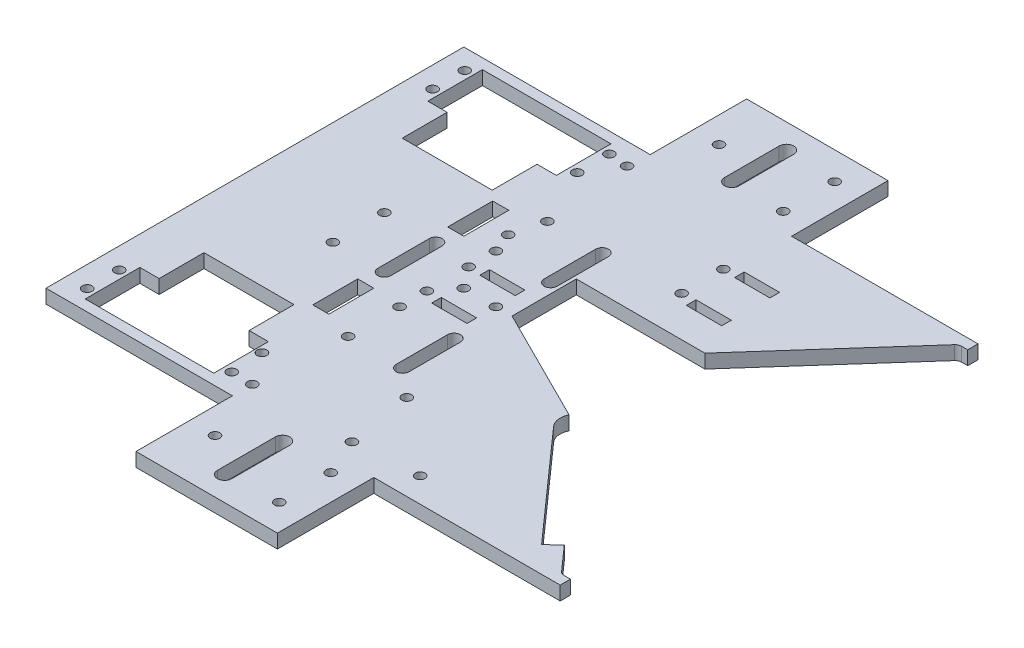
SolidWorks part; units mm, degrees
material "Acrylic (Medium-high impact)"
ref_plane "Front Plane" through (0, 0, 0) normal (0, 0, 1) x (1, 0, 0)
ref_plane "Top Plane" through (0, 0, 0) normal (0, 1, 0) x (1, 0, 0)
ref_plane "Right Plane" through (0, 0, 0) normal (1, 0, 0) x (0, 0, -1)
sketch "Sketch2" plane through (0, 0, 0) normal (0, 1, 0) x (1, 0, 0)
  line L2 (0, 0) -> (0, 65)
  line L3 (0, 65) -> (58, 65)
  line L4 (160, 0) -> (160, 65)
  line L8 (0, 0) -> (160, 0)
  line L9 (102, 65) -> (160, 65)
  line L11 (102, 65) -> (102, 95)
  line L12 (58, 65) -> (58, 95)
  line L13 (58, 95) -> (102, 95)
  dimension "D1" = 65
  dimension "D2" = 160
  dimension "D3" = 44
  dimension "D4" = 30
extrude "Boss-Extrude1" add sketch "Sketch2" along normal blind 4.3
mirror "Mirror1" about plane through (0, 4.3, 0) normal (0, 0, -1) of bodies 101
sketch "Sketch3" plane through (0, 4.3, 0) normal (0, 1, 0) x (1, 0, 0)
  line L0 (160, 61.8) -> (160, -61.8)
  line L1 (120.0126, 20) -> (157.1565, 61.8)
  line L3 (80.0126, 0) -> (80.0126, 20)
  line L4 (80.0126, 20) -> (120.0126, 20)
  line L12 (160, 65) -> (102, 65)
  line L13 (102, 65) -> (102, 95)
  line L15 (102, 95) -> (58, 95)
  line L16 (58, 65) -> (0, 65)
  line L17 (0, 65) -> (0, -65)
  line L18 (0, -65) -> (58, -65)
  line L20 (58, 95) -> (58, 65)
  line L22 (102, -65) -> (160, -65)
  line L23 (160, -65) -> (160, 65)
  line L36 (58, -65) -> (58, -95)
  line L38 (58, -95) -> (102, -95)
  line L39 (58, -95) -> (102, -95)
  line L40 (102, -95) -> (102, -65)
  line L42 (160, -61.8) -> (157.1556, -61.8)
  line L45 (160, 61.8) -> (157.1565, 61.8)
  line L48 (80.0126, 0) -> (120, -20)
  line L49 (120, -20) -> (157.1556, -61.8)
  line M24 (160, -65) -> (160, 65)
  dimension "D2" = 130
  dimension "D3" = 20
  dimension "D4" = 40
  dimension "D1" = 0
extrude "Cut-Extrude1" cut sketch "Sketch3" against normal blind 4.5 contours L48 L49 L1 L4 L3 M24 region at (132.7054, 4.3, -1.1594)
fillet "Fillet1" radius 2 2 edges at (157.1565, 2.15, -61.8) (157.1556, 2.15, 61.8)
ref_axis "Axis1" through (80, 4.3, 95) along (0, 0, -1)
sketch "Sketch4" plane through (0, 4.3, 0) normal (0, 1, 0) x (1, 0, 0)
  line L0 (80, -95) -> (80, 95)
  line L1 (102, -95) -> (58, -95) construction
  line L2 (102, 95) -> (58, 95) construction
ref_plane "Plane2" through (0, 4.3, 0) normal (0, 1, 0) x (1, 0, 0)
sketch "Sketch6" plane through (0, 4.3, 0) normal (0, 1, 0) x (1, 0, 0)
  line L3 (9, -61.8) -> (49, -61.8)
  line L6 (29, -45.8) -> (29, -44.8)
  line L7 (9, -44.8) -> (15, -44.8)
  line L11 (43, -44.8) -> (43, -30.8418)
  line L12 (15, -44.8) -> (15, -30.8418)
  line L13 (15, -30.8418) -> (43, -30.8418)
  line L15 (0, 0) -> (80.0126, 0)
  line L16 (80.0126, 0) -> (120, -20) construction
  line L18 (9, 44.8) -> (15, 44.8)
  line L20 (15, 30.8418) -> (43, 30.8418)
  line L21 (15, 44.8) -> (15, 30.8418)
  line L22 (43, 44.8) -> (43, 30.8418)
  line L25 (15, -45.8) -> (15, -30.8418) construction
  line L27 (9, 61.8) -> (49, 61.8)
  line L30 (4, -61.8) -> (3, -61.8)
  line L31 (0, -61.8) -> (160, -61.8) construction
  line L32 (3, -61.8) -> (4, -61.8)
  line L33 (3, -44.8) -> (3, -62.8) construction
  line L34 (3, -62.8) -> (55, -62.8) construction
  line L35 (55, -44.8) -> (55, -62.8) construction
  line L36 (4, -61.8) -> (54, -61.8) construction
  line L37 (0, 61.8) -> (160, 61.8) construction
  line L38 (54, 61.8) -> (55, 61.8)
  line L39 (54, 61.8) -> (55, 61.8)
  line L40 (43, 44.8) -> (49, 44.8)
  line L41 (4, -45.8) -> (4, -61.8) construction
  line L42 (4, -45.8) -> (54, -45.8) construction
  line L43 (43, -44.8) -> (49, -44.8)
  line L44 (3, -44.8) -> (55, -44.8) construction
  line L45 (29, -45.8) -> (29, -30.8418) construction
  line L46 (43, -45.8) -> (43, -30.8418) construction
  line L47 (54, -45.8) -> (54, -61.8) construction
  line L48 (9, -61.8) -> (49, -61.8)
  line L52 (9, 61.8) -> (9, 44.8)
  line L53 (55, 61.8) -> (54, 61.8)
  line L56 (49, 61.8) -> (49, 44.8)
  line L59 (3, -61.8) -> (4, -61.8)
  line L60 (9, -44.8) -> (9, -61.8)
  line L64 (49, -44.8) -> (49, -61.8)
  dimension "D4" = 1
  dimension "D5" = 14
  dimension "D6" = 14
extrude "Cut-Extrude2" cut sketch "Sketch6" against normal blind 10
sketch "Sketch8" plane through (0, 4.3, 0) normal (0, 1, 0) x (1, 0, 0)
  circle A0 centre (6.5, 58.8) radius 1.5
  circle A1 centre (6.5, 48.8) radius 1.5
  circle A2 centre (51.5, 48.8) radius 1.5
  circle A3 centre (51.5, 58.8) radius 1.5
  circle A4 centre (6.5, -48.7) radius 1.5
  circle A5 centre (6.5, -58.7) radius 1.5
  circle A6 centre (51.5, -58.7) radius 1.5
  circle A7 centre (51, -48.8) radius 1.5
  dimension "D7" = 3
extrude "Cut-Extrude3" cut sketch "Sketch8" against normal blind 10
sketch "Sketch9" plane through (0, 0, 0) normal (0, -1, 0) x (1, 0, 0)
  line L0 (75.75, 69.4) -> (75.75, 87.4)
  line L1 (75.75, -87.4) -> (75.75, -70.4)
  line L2 (80.25, -87.4) -> (80.25, -70.4)
  line L4 (80.25, 69.4) -> (80.25, 87.4)
  circle A0 centre (94, 70.4) radius 1.5
  circle A1 centre (66, 78.4) radius 1.5
  circle A2 centre (66, -78.4) radius 1.5
  circle A3 centre (94, -86.4) radius 1.5
  circle A4 centre (94, 86.4) radius 1.5
  circle A5 centre (94, -70.4) radius 1.5
  arc A6 (75.75, -87.4) -> (80.25, -87.4) centre (78, -87.4) ccw
  arc A7 (80.25, -70.4) -> (75.75, -70.4) centre (78, -70.4) ccw
  arc A10 (75.75, 69.4) -> (80.25, 69.4) centre (78, 69.4) ccw
  arc A12 (80.25, 87.4) -> (75.75, 87.4) centre (78, 87.4) ccw
  dimension "D1" = 3
extrude "Cut-Extrude4" cut sketch "Sketch9" against normal blind 10
sketch "Sketch7" plane through (0, 4.3, 0) normal (0, 1, 0) x (1, 0, 0)
  line L0 (0, 0) -> (80.0126, 0)
  line L1 (0, 65) -> (0, -65) construction
  line L2 (80.0126, 0) -> (80.0126, 20) construction
  line L3 (80, -95) -> (80, 95) construction
  line L4 (64, -9) -> (75, -9)
  line L5 (64, -6) -> (75, -6)
  line L6 (64, -9) -> (64, -6)
  line L7 (75, -9) -> (75, -6)
  line L8 (64, -7.5) -> (75, -7.5)
  line L9 (64, 7.5) -> (75, 7.5)
  line L10 (75, 9) -> (75, 6)
  line L11 (64, 9) -> (64, 6)
  line L12 (64, 6) -> (75, 6)
  line L13 (64, 9) -> (75, 9)
  line L14 (104.2547, 30) -> (115.2547, 30)
  line L15 (104.2547, 33) -> (115.2547, 33)
  line L16 (104.2547, 30) -> (104.2547, 33)
  line L17 (115.2547, 30) -> (115.2547, 33)
  line L20 (115.2547, 48) -> (115.2547, 45)
  line L21 (104.2547, 48) -> (104.2547, 45)
  line L22 (104.2547, 45) -> (115.2547, 45)
  line L23 (104.2547, 48) -> (115.2547, 48)
  line L24 (80.0126, 20) -> (120.0126, 20) construction
  circle A0 centre (60.0126, -6.5) radius 1.5
  circle A1 centre (60.0126, 6.5) radius 1.5
  circle A2 centre (100.2673, 32.5) radius 1.5
  circle A3 centre (100.2673, 45.5) radius 1.5
  dimension "D1" = 3
  dimension "D8" = 3
  dimension "D2" = 6.5
  dimension "D3" = 20
  dimension "D6" = 11
  dimension "D4" = 5
  dimension "D5" = 3
  dimension "D7" = 7.5
  dimension "D9" = 11
  dimension "D10" = 3
  dimension "D11" = 12
  dimension "D12" = 13
  dimension "D13" = 10
  dimension "D14" = 3.9874
  dimension "D15" = 0.5
  dimension "D16" = 0.5
  dimension "D17" = 3.9874
sketch "Sketch10" plane through (0, 4.3, 0) normal (0, 1, 0) x (1, 0, 0)
  line L0 (120, -20) -> (156.5589, -61.1287) construction
  line L1 (123.3218, -23.737) -> (149.8964, -53.6334)
  line L2 (116.263, -23.3218) -> (146.1593, -56.9552)
  line L3 (149.8964, -53.6334) -> (146.1593, -56.9552)
  line L4 (120, -20) -> (156.5589, -61.1287) construction
  line L5 (116.263, -23.3218) -> (152.8218, -64.4505) construction
  arc A0 (123.3218, -23.737) -> (116.263, -23.3218) centre (120, -20) ccw
  dimension "D1" = 5
  dimension "D2" = 45
extrude "Cut-Extrude5" cut sketch "Sketch10" against normal blind 10
sketch "Sketch11" plane through (0, 0, 0) normal (0, -1, 0) x (1, 0, 0)
  line L0 (0, 0) -> (80.0126, 0) construction
  line L1 (80, 95) -> (80, -95) construction
  line L2 (80.0126, 0) -> (0, 0)
  line L4 (75, 31.0313) -> (75, 15.0313)
  line L6 (79, 31.0313) -> (79, 15.0313)
  line L7 (79, -31.0313) -> (79, -15.0313)
  line L8 (75, -31.0313) -> (75, -15.0313)
  circle A0 centre (60, 31) radius 1.5
  circle A1 centre (60, 15) radius 1.5
  arc A2 (75, 31.0313) -> (79, 31.0313) centre (77, 31.0313) cw
  arc A3 (75, 15.0313) -> (79, 15.0313) centre (77, 15.0313) ccw
  arc A4 (75, -15.0313) -> (79, -15.0313) centre (77, -15.0313) cw
  arc A5 (75, -31.0313) -> (79, -31.0313) centre (77, -31.0313) ccw
  circle A6 centre (60, -15) radius 1.5
  circle A7 centre (60, -31) radius 1.5
  dimension "D1" = 3
  dimension "D2" = 16
  dimension "D3" = 15
  dimension "D4" = 20
  dimension "D5" = 15
  dimension "D6" = 4
extrude "Cut-Extrude6" cut sketch "Sketch11" against normal blind 10 contours L4 A3 L6 A2 | L8 A5 L7 A4 | A7 | A0 | A1 | A6 region at (77, 0, 23.0313) region at (77, 0, -23.0313) region at (60, 0, -31)
sketch "Sketch12" plane through (0, 0, 0) normal (0, -1, 0) x (-1, 0, 0)
  line L0 (0, 0) -> (-80.0126, 0) construction
  line L3 (-50.2627, -8) -> (-50.2627, 8)
  line L4 (-50.2627, 0) -> (-46.2627, 0)
  line L5 (-46.2627, -8) -> (-46.2627, 8)
  line L6 (0, 0) -> (-46.2627, 0)
  line L7 (0, 65) -> (0, -65) construction
  line L8 (-160, -61.8) -> (0, -61.8) construction
  line L9 (-80.0126, 0) -> (-50.2627, 0)
  line L10 (-80.0126, 0) -> (-115.5281, -17.7634) construction
  line L11 (-80.0126, 0) -> (-80.0126, 20) construction
  line L12 (-58, -65) -> (0, -65) construction
  line L13 (-58, 65) -> (0, 65) construction
  circle A0 centre (-32.2627, -8) radius 1.5
  circle A1 centre (-32.2627, 8) radius 1.5
  arc A2 (-46.2627, 8) -> (-50.2627, 8) centre (-48.2627, 8) ccw
  arc A3 (-50.2627, -8) -> (-46.2627, -8) centre (-48.2627, -8) ccw
  circle A5 centre (-32.2627, -8) radius 1.5 construction
  circle A6 centre (-32.2627, 8) radius 1.5 construction
  dimension "D1" = 3
  dimension "D8" = 8
  dimension "D9" = 8
  dimension "D2" = 8
  dimension "D3" = 14
  dimension "D4" = 4
  dimension "D5" = 61.8
  dimension "D6" = 65
  dimension "D7" = 65
extrude "Cut-Extrude7" cut sketch "Sketch12" against normal blind 10 contours A3 L5 L4 L3 | L4 L5 A2 L3 | A0 | A1 region at (48.2627, 0, 4.7958) region at (48.2627, 0, -4.7958) region at (32.2627, 0, 8) region at (32.2627, 0, -8)
extrude "Cut-Extrude8" cut sketch "Sketch7" against normal blind 9 contours A0 | L4 L7 L5 L6 | L12 L10 L13 L11 | A1 | L23 L20 L22 L21 | L15 L17 L14 L16 | A3 | A2
sketch "Sketch13" plane through (0, 4.3, 0) normal (0, 1, 0) x (1, 0, 0)
  line L0 (80.0126, 0) -> (59.0194, 0)
  line L1 (80, -95) -> (80, 95) construction
  circle A0 centre (65, 0) radius 1.5
  circle A1 centre (75, 0) radius 1.5
  dimension "D2" = 3
  dimension "D3" = 5
  dimension "D1" = 10
extrude "Cut-Extrude9" cut sketch "Sketch13" against normal blind 10 contours L0 A0 | L0 A0 | L0 A1 | L0 A1 region at (75, 4.3, 0.6366) region at (75, 4.3, -0.6366) region at (65, 4.3, 0.6366) region at (65, 4.3, -0.6366)
sketch "Sketch14" plane through (0, 4.3, 0) normal (0, 1, 0) x (1, 0, 0)
  circle A0 centre (57.5, 58.3) radius 1.5
  circle A2 centre (57.5, 21.3) radius 1.5
  circle A3 centre (85.5653, -38.3098) radius 1.5
  circle A4 centre (108.7541, -57.3434) radius 1.5
  dimension "D1" = 3
  dimension "D2" = 3
extrude "Cut-Extrude10" cut sketch "Sketch14" against normal blind 10
sketch "Sketch15" plane through (0, 4.3, 0) normal (0, 1, 0) x (1, 0, 0)
  line L1 (46, 28) -> (51, 28)
  line L2 (46, 28) -> (46, 14)
  line L3 (46, 14) -> (51, 14)
  line L4 (51, 28) -> (51, 14)
  line L6 (0, 65) -> (0, -65) construction
  line L7 (80.0126, 0) -> (53.7017, 0)
  line L8 (46, -14) -> (51, -14)
  line L9 (51, -28) -> (51, -14)
  line L10 (46, -28) -> (51, -28)
  line L11 (46, -28) -> (46, -14)
  arc A0 (50.2627, 8) -> (46.2627, 8) centre (48.2627, 8) ccw construction
  arc A1 (46.2627, -8) -> (50.2627, -8) centre (48.2627, -8) ccw construction
  dimension "D1" = 46
  dimension "D2" = 5
  dimension "D3" = 14
  dimension "D4" = 14
  dimension "D5" = 14
  dimension "D6" = 6
  dimension "D7" = 6
extrude "Cut-Extrude11" cut sketch "Sketch15" against normal blind 10 contours L4 L1 L2 L3 | L11 L10 L9 L8 region at (48.5, 4.3, -21) region at (48.5, 4.3, 21)
sketch "Sketch16" plane through (0, 4.3, 0) normal (0, 1, 0) x (1, 0, 0)
  circle A0 centre (89, -58.8) radius 1.5
  circle A1 centre (58, -58.8) radius 1.5
  dimension "D1" = 3
extrude "Cut-Extrude12" cut sketch "Sketch16" against normal blind 10
ref_plane "Plane3" through (44.2426, 0, 0) normal (1, 0, 0) x (0, 0, -1)
sketch "Sketch17" plane through (44.2426, 0, 0) normal (1, 0, 0) x (0, 0, -1)
  line L4 (0, 0) -> (20, 0)
  line L5 (20, 0) -> (20, 4.3)
  line L6 (20, 4.3) -> (0, 4.3)
  line L7 (0, 4.3) -> (0, 0)
  line L8 (0, 0) -> (20, 0)
  line L9 (20, 0) -> (20, 4.3)
  line L10 (20, 4.3) -> (0, 4.3)
  line L11 (0, 4.3) -> (0, 0)
  circle A0 centre (-2.83, 16.28) radius 0.5
  point P6 (0, 2.15)
  dimension "D4" = 1
  dimension "D2" = 2.83
  dimension "D3" = 14.13
  dimension "D1" = 0
